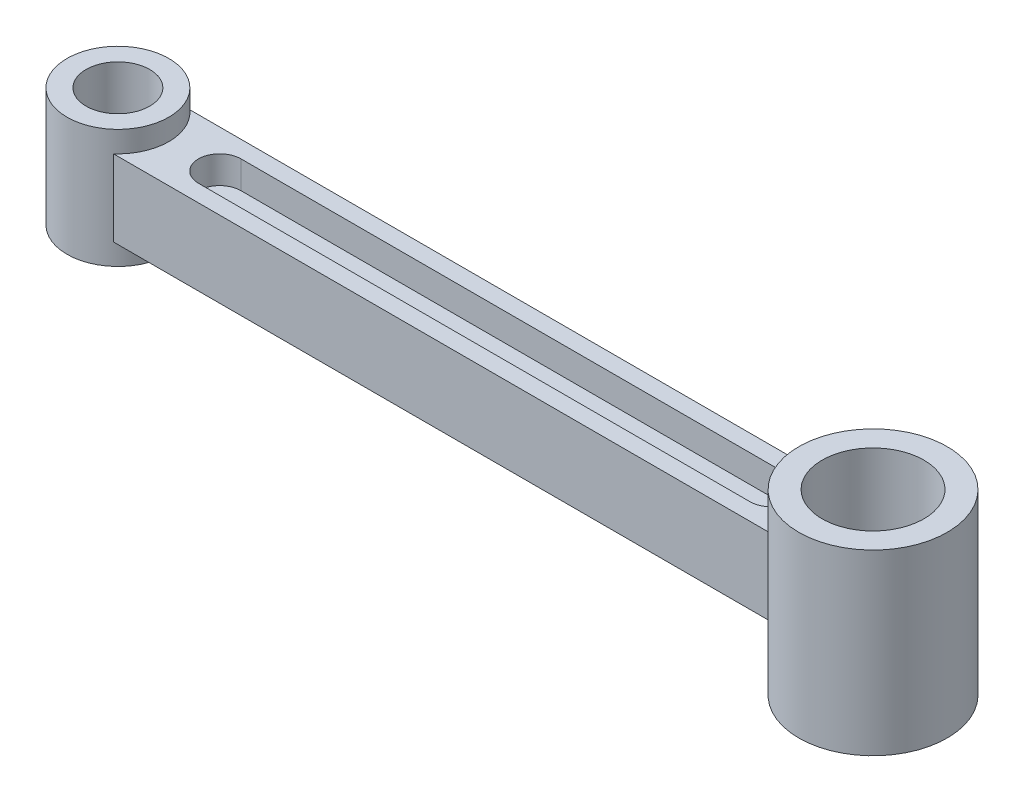
SolidWorks part; units mm, degrees
ref_plane "Front Plane" through (0, 0, 0) normal (0, 0, 1) x (1, 0, 0)
ref_plane "Top Plane" through (0, 0, 0) normal (0, 1, 0) x (1, 0, 0)
ref_plane "Right Plane" through (0, 0, 0) normal (1, 0, 0) x (0, 0, -1)
sketch "Sketch1" plane through (0, 0, 0) normal (0, 1, 0) x (1, 0, 0)
  line L0 (0, 0) -> (25327.2534, 0) construction
  line L1 (38.1295, 9) -> (50038.1295, 9) construction
  line L2 (7.9373, 9) -> (162.9917, 9)
  line L3 (7.9373, -9) -> (162.9917, -9)
  circle A0 centre (0, 0) radius 12
  circle A1 centre (0, 0) radius 7.5
  circle A2 centre (178, 0) radius 17.5
  circle A3 centre (178, 0) radius 12
  dimension "D1" = 24
  dimension "D2" = 15
  dimension "D3" = 35
  dimension "D4" = 24
  dimension "D5" = 178
  dimension "D6" = 9
extrude "Boss-Extrude1" add sketch "Sketch1" along normal mid plane 28 contours A0 A1 region at (10.6279, 0, -4.7976)
extrude "Boss-Extrude4" add sketch "Sketch1<6>" along normal mid plane 42 separate body contours A2 A3 region at (182.5372, 0, -16.3886)
sketch "Sketch1<6>" plane through (0, 0, 0) normal (0, 1, 0) x (1, 0, 0) same geometry as "Sketch1"
extrude "Boss-Extrude5" add sketch "Sketch1<7>" along normal mid plane 18 contours A2 L2 A0 L3 region at (86.0265, 0, 0)
sketch "Sketch1<7>" plane through (0, 0, 0) normal (0, 1, 0) x (1, 0, 0) same geometry as "Sketch1"
sketch "Sketch3" plane through (0, 0, 0) normal (0, 1, 0) x (1, 0, 0)
  line L0 (24, 0) -> (154, 0) construction
  line L1 (24, 5) -> (154, 5)
  line L2 (24, -5) -> (154, -5)
  arc A0 (24, 5) -> (24, -5) centre (24, 0) ccw
  arc A1 (154, -5) -> (154, 5) centre (154, 0) ccw
  point P3 (89, 0)
  point P9 (178, 0)
  dimension "D1" = 130
  dimension "D2" = 10
  dimension "D3" = 24
  dimension "D4" = 24
extrude "Cut-Extrude2" cut sketch "Sketch3" against normal blind 18 from offset 2.5 contours L1 A1 L2 A0 offset against normal yes
mirror "Mirror2" about plane through (0, 0, 0) normal (0, 1, 0) of "Cut-Extrude2"
